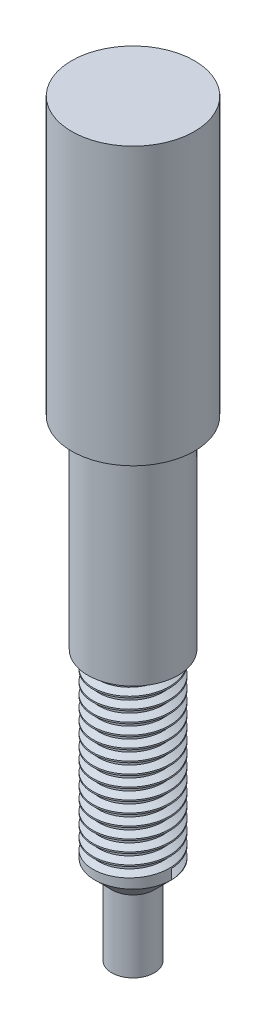
SolidWorks part; units mm, degrees
ref_plane "Front Plane" through (0, 0, 0) normal (0, 0, 1) x (1, 0, 0)
ref_plane "Top Plane" through (0, 0, 0) normal (0, 1, 0) x (1, 0, 0)
ref_plane "Right Plane" through (0, 0, 0) normal (1, 0, 0) x (0, 0, -1)
sketch "Sketch2" plane through (0, 0, 0) normal (0, 0, 1) x (1, 0, 0)
  line L0 (0, 0) -> (0, 508.8276) construction
  line L1 (0, 0) -> (6, 0)
  line L2 (0, 0) -> (0, 25.4)
  line L3 (0, 25.4) -> (6, 25.4)
  line L4 (6, 0) -> (6, 25.4)
  line L5 (0, 25.4) -> (10.8102, 25.4)
  line L6 (0, 25.4) -> (0, 76.2)
  line L7 (0, 76.2) -> (10.8102, 76.2)
  line L8 (10.8102, 25.4) -> (10.8102, 76.2)
  line L9 (0, 76.2) -> (12.7635, 76.2)
  line L10 (0, 76.2) -> (0, 133.35)
  line L11 (0, 133.35) -> (12.7635, 133.35)
  line L12 (12.7635, 76.2) -> (12.7635, 133.35)
  line L13 (0, 133.35) -> (17.3461, 133.35)
  line L14 (0, 133.35) -> (0, 211.582)
  line L15 (0, 211.582) -> (17.3461, 211.582)
  line L16 (17.3461, 133.35) -> (17.3461, 211.582)
  dimension "D1" = 78.232
  dimension "D2" = 17.3461
  dimension "D4" = 57.15
  dimension "D3" = 12.7635
  dimension "D5" = 50.8
  dimension "D6" = 10.8102
  dimension "D7" = 25.4
  dimension "D8" = 6
revolve "Revolve1" add sketch "Sketch2" angle 360 about L0 region at (3, 12.7, 0) region at (5.4051, 50.8, 0) region at (6.3817, 104.775, 0) region at (8.673, 172.466, 0)
chamfer "Chamfer1" distance 5.08 angle 45 1 edges at (0, 25.4, -6)
thread "Thread1" pitch 3.175 method cut profile "Thread Profile1" start angle 0, offset 0, length 0, pitch 3.175, diameter 21.6205
ref_plane "Plane1" through (10.8102, 25.1302, 0) normal (0, 0, 1) x (1, 0, 0)
sketch "Thread Profile1" plane through (10.8102, 25.1302, 0) normal (0, 0, 1) x (1, 0, 0)
  line L0 (0, 0) -> (0, 3.175) construction
  line L11 (0, 0) -> (0, 2.7781)
  line L12 (0, 2.7781) -> (-1.7185, 1.7859)
  line L13 (-1.7185, 1.7859) -> (-1.7185, 0.9922)
  line L15 (-1.7185, 0.9922) -> (0, 0)
  line L17 (-1.7185, 1.3891) -> (0, 1.3891) construction
  point P2 (0, 0)
  dimension "Pitch" = 3.175
  dimension "Profile_Angle" = 60
  dimension "Profile_Land" = 0.7937
  dimension "Profile_Height" = 1.7185
equation "\"hole diamiter\"= 1.36in"
equation "\"wheel depth\"= 2.88"
equation "\"press_to_wheel\"= 0.005 * sqr ( \"hole diamiter\" )"
equation "\"wheel_connection\"= \"hole diamiter\" + \"press_to_wheel\"'https://at-machining.com/tolerance-press-fit/"
equation "\"D1@Sketch2\"=\"wheel depth\"+0.2"
equation "\"D2@Sketch2\"=\"wheel_connection\"/2"
equation "\"fitting depth\"= 2.25"
equation "\"D4@Sketch2\"=\"fitting depth\""
equation "\"bearing_id\"= 1"
equation "\"bearing_connection\"= 0.005 * sqr ( \"bearing_id\" ) + \"bearing_id\"'https://at-machining.com/tolerance-press-fit/"
equation "\"D3@Sketch2\"=\"bearing_connection\"/2"
equation "\"thread length\"= 2"
equation "\"minor_diamiter\"= 0.8512in'https://www.machiningdoctor.com/threadinfo/?tid=109"
equation "\"D5@Sketch2\"=\"thread length\""
equation "\"D6@Sketch2\"=\"minor_diamiter\"/2"
equation "\"coupling diamiter\"= 12mm"
equation "\"coupling lenght\"=1"
equation "\"D7@Sketch2\"=\"coupling lenght\""
equation "\"D8@Sketch2\"=\"coupling diamiter\"/2"
